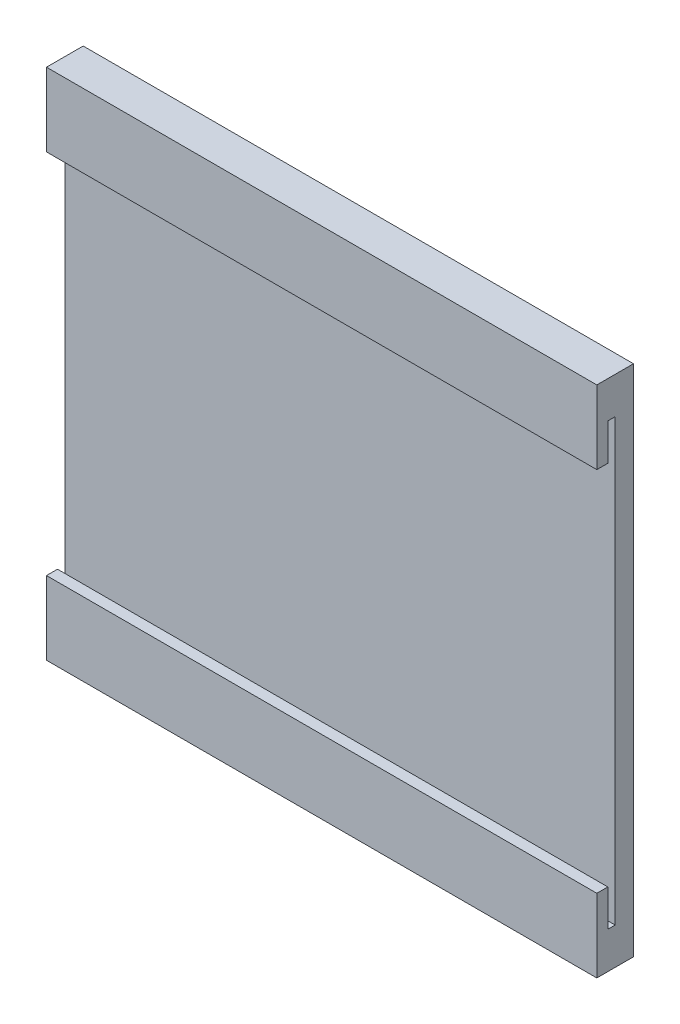
SolidWorks part; units mm, degrees
ref_plane "Front Plane" through (0, 0, 0) normal (0, 0, 1) x (1, 0, 0)
ref_plane "Top Plane" through (0, 0, 0) normal (0, 1, 0) x (1, 0, 0)
ref_plane "Right Plane" through (0, 0, 0) normal (1, 0, 0) x (0, 0, -1)
sketch "Sketch1" plane through (0, 0, 0) normal (0, 0, 1) x (1, 0, 0)
  line L0 (0, 60) -> (150, 60)
  line L1 (0, 70) -> (150, 70)
  line L2 (0, 70) -> (0, -70)
  line L3 (0, -70) -> (150, -70)
  line L4 (150, 70) -> (150, -70)
  line L5 (0, 50) -> (150, 50)
  line L6 (0, -60) -> (150, -60)
  line L7 (0, -50) -> (150, -50)
  dimension "D1" = 140
  dimension "D2" = 150
  dimension "D3" = 20
  dimension "D4" = 10
  dimension "D5" = 20
  dimension "D6" = 10
extrude "Boss-Extrude1" add sketch "Sketch1" along normal blind 10 contours L2 L5 L4 L0 | L4 L1 L2 L0 | L7 L2 L6 L4 | L6 L2 L3 L4 | L2 L7 L4 L5 region at (75, 65, 0) region at (75, 55, 0) region at (75, 0, 0) region at (75, -55, 0) region at (75, -65, 0)
extrude "Cut-Extrude1" cut sketch "Sketch1<3>" along normal through all from offset 5 contours L2 L7 L4 L5 region at (75, 0, 0)
sketch "Sketch1<3>" plane through (0, 0, 0) normal (0, 0, 1) x (1, 0, 0) same geometry as "Sketch1"
extrude "Cut-Extrude2" cut sketch "Sketch1<4>" along normal blind 2 from offset 5 contours L2 L5 L4 L0 | L7 L2 L6 L4 region at (75, 55, 0) region at (75, -55, 0)
sketch "Sketch1<4>" plane through (0, 0, 0) normal (0, 0, 1) x (1, 0, 0) same geometry as "Sketch1"
